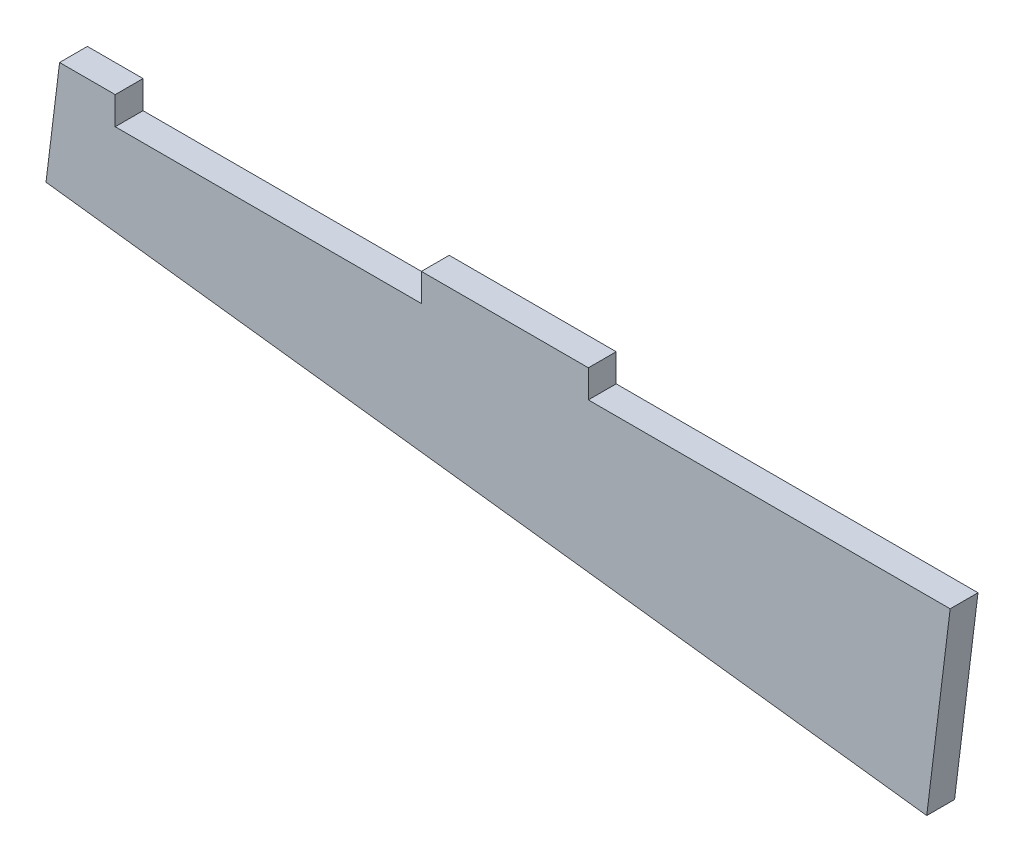
SolidWorks part; units mm, degrees
ref_plane "Front Plane" through (0, 0, 0) normal (0, 0, 1) x (1, 0, 0)
ref_plane "Top Plane" through (0, 0, 0) normal (0, 1, 0) x (1, 0, 0)
ref_plane "Right Plane" through (0, 0, 0) normal (1, 0, 0) x (0, 0, -1)
sketch "Sketch1" plane through (0, 0, 0) normal (0, 0, 1) x (1, 0, 0)
  line L0 (-195.3168, -62.6592) -> (-182.6168, -62.6592)
  line L4 (-182.6168, -62.6592) -> (-182.6168, -69.0092)
  line L5 (-182.6168, -69.0092) -> (-112.7668, -69.0092)
  line L6 (-112.7668, -69.0092) -> (-112.7668, -62.6592)
  line L7 (-112.7668, -62.6592) -> (-74.6668, -62.6592)
  line L8 (-74.6668, -62.6592) -> (-74.6668, -69.0092)
  line L9 (-74.6668, -69.0092) -> (7.8832, -69.0092)
  line L10 (7.8832, -69.0092) -> (2.5379, -112.5435)
  line L11 (2.5379, -112.5435) -> (-198.4122, -87.8699)
  line L12 (-198.4122, -87.8699) -> (-195.3168, -62.6592)
  line L13 (-387.3613, -17.3642) -> (-31.7613, -61.0264) construction
  dimension "D1" = 12.7
  dimension "D2" = 6.35
  dimension "D3" = 69.85
  dimension "D4" = 38.1
  dimension "D5" = 82.55
  dimension "D6" = 25.4
extrude "Boss-Extrude1" add sketch "Sketch1" against normal blind 6.35
